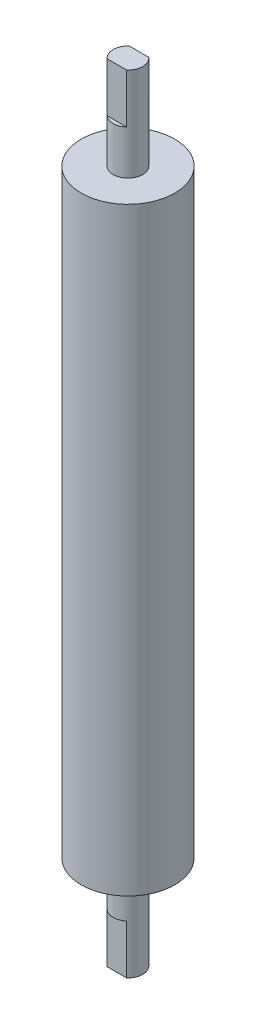
SolidWorks part; units mm, degrees
material "Alloy Steel"
ref_plane "X-Y Datum" through (0, 0, 0) normal (0, 0, 1) x (1, 0, 0)
ref_plane "X-Z Datum" through (0, 0, 0) normal (0, 1, 0) x (1, 0, 0)
ref_plane "Y-Z Datum" through (0, 0, 0) normal (1, 0, 0) x (0, 0, -1)
sketch "Sketch1" plane through (0, 0, 0) normal (0, 1, 0) x (1, 0, 0)
  circle A0 centre (0, 0) radius 3.175
  dimension "D1" = 6.35
extrude "Boss-Extrude1" add sketch "Sketch1" along normal blind 20.32 and the other way blind 20.32
sketch "Sketch2" plane through (0, 20.32, 0) normal (0, 1, 0) x (1, 0, 0)
  circle A0 centre (0, 0) radius 1
  dimension "D1" = 2
extrude "Boss-Extrude2" add sketch "Sketch2" along normal blind 6.35
ref_plane "Plane1" through (0, 23.32, 0) normal (0, 1, 0) x (1, 0, 0)
sketch "Sketch3" plane through (0, 23.32, 0) normal (0, 1, 0) x (1, 0, 0)
  line L1 (-1.6764, -0.75) -> (1.6764, -0.75)
  line L2 (-1.6764, -0.75) -> (-1.6764, 0.75)
  line L3 (-1.6764, 0.75) -> (1.6764, 0.75)
  line L4 (1.6764, -0.75) -> (1.6764, 0.75)
  line L5 (-1.6764, -0.75) -> (1.6764, 0.75) construction
  line L6 (-1.6764, 0.75) -> (1.6764, -0.75) construction
  circle A0 centre (0, 0) radius 1
  point P0 (0, 0)
  dimension "D1" = 1.5
extrude "Cut-Extrude1" cut sketch "Sketch3" along normal blind 6.35 contours L3 A0 | L1 A0 region at (0, 23.32, 0.8512) region at (0, 23.32, -0.8512)
mirror "Mirror1" about plane through (0, 0, 0) normal (0, 1, 0) of "Cut-Extrude1", "Boss-Extrude2"
